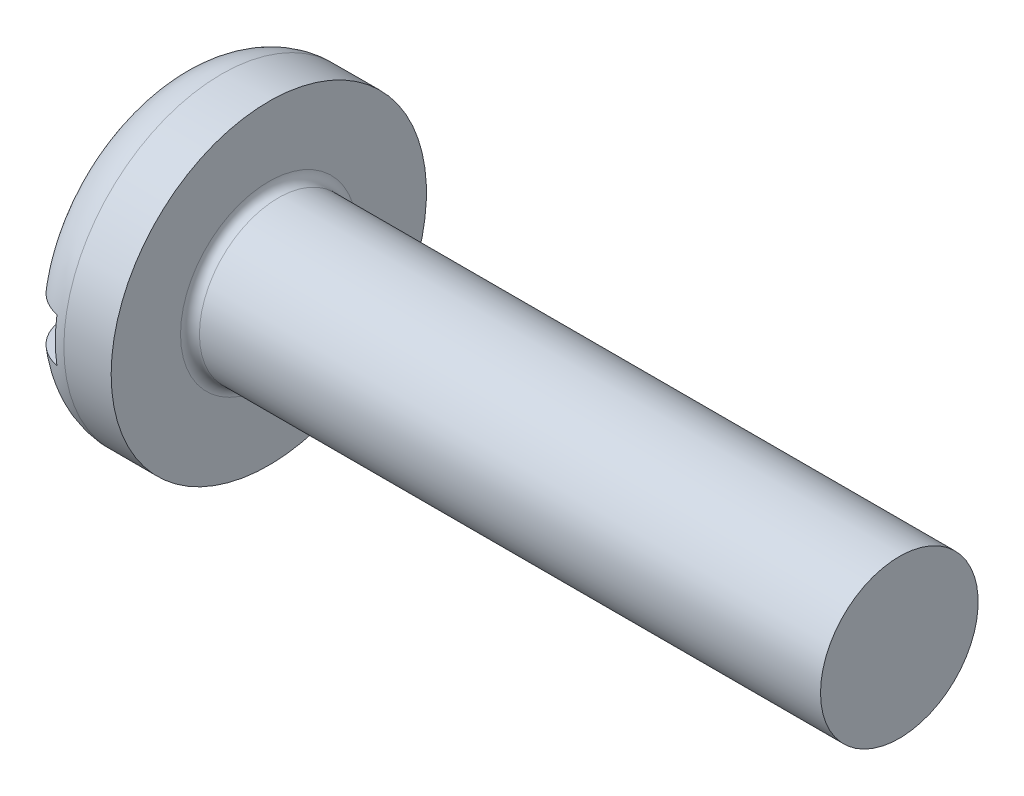
SolidWorks part; units mm, degrees
ref_plane "Front Plane" through (0, 0, 0) normal (0, 0, 1) x (1, 0, 0)
ref_plane "Top Plane" through (0, 0, 0) normal (0, 1, 0) x (1, 0, 0)
ref_plane "Right Plane" through (0, 0, 0) normal (1, 0, 0) x (0, 0, -1)
sketch "BodySke" plane through (0, 0, 0) normal (0, 0, 1) x (1, 0, 0)
  line L0 (0, 0) -> (111.3824, 0) construction
  line L1 (0, 0) -> (0, 10)
  line L2 (0, 10) -> (6, 10)
  line L3 (6, 10) -> (6, 5)
  line L4 (6, 5) -> (46, 5)
  line L5 (46, 5) -> (46, 0)
  line L6 (7.5, 8.824) -> (7.5, -5.8939) construction
  line L7 (0, 0) -> (46, 0)
  line L8 (9, 8.824) -> (9, -5.8939) construction
  point P10 (46, 4.172)
  dimension "Thread_minor" = 8.344
  dimension "Advance" = 1.5
revolve "BaseBody" add sketch "BodySke" angle 360 about L0
cosmetic thread "ThreadCosmetic" [suppressed] parameters "Thread_minor"=8.344
fillet "Fillet_head" radius 3 1 edges at (0, 0, 10)
fillet "Fillet2" radius 0.6 1 edges at (6, 0, 5)
sketch "SlotSke" plane through (0, 0, 0) normal (-1, 0, 0) x (0, 0, 1)
  line L1 (-10, 1.405) -> (10, 1.405)
  line L2 (-10, 1.405) -> (-10, -1.405)
  line L3 (-10, -1.405) -> (10, -1.405)
  line L4 (10, 1.405) -> (10, -1.405)
  dimension "D1" = 20
  dimension "D2" = 10
  dimension "D3" = 1.405
extrude "Slot" cut sketch "SlotSke" against normal blind 2.4
sketch "ThdSchSke" plane through (0, 0, 0) normal (0, 0, 1) x (1, 0, 0)
  line L0 (0, 0) -> (55.1256, 0) construction
  line L1 (0, 0) -> (111.3824, 0) construction
  line L2 (45.522, 5) -> (45.522, 5.9561)
  line L3 (45.522, 5.9561) -> (46.478, 5.9561)
  line L4 (46.478, 5.9561) -> (46.478, 5)
  line L5 (46.478, 5) -> (46, 4.172)
  line L6 (46, 4.172) -> (45.522, 5)
  line L7 (6, 5) -> (46, 5) construction
  line L13 (46, 5) -> (46, 0) construction
revolve "ThreadSchematic" [suppressed] cut sketch "ThdSchSke" angle 360 about L0
pattern_linear "ThdSchPat" [suppressed] count 25 along (-1, 0, 0) of bodies 103
equation "\"Thread_minor@ThreadCosmetic\" = \"Thread_minor@BodySke\""
equation "\"D1@SlotSke\" = \"Head_dia@BodySke\""
equation "\"D2@SlotSke\" = \"D1@SlotSke\" / 2"
equation "\"D3@SlotSke\" = \"Slot_width@SlotSke\" / 2"
equation "\"Advance@ThdSchPat\" = \"Advance@BodySke\""
equation "\"D1@ThdSchPat\" =  int(  ( \"Length@BodySke\"-\"Thread_runout@BodySke\" )  /\"Advance@ThdSchPat\" )  + 1"
